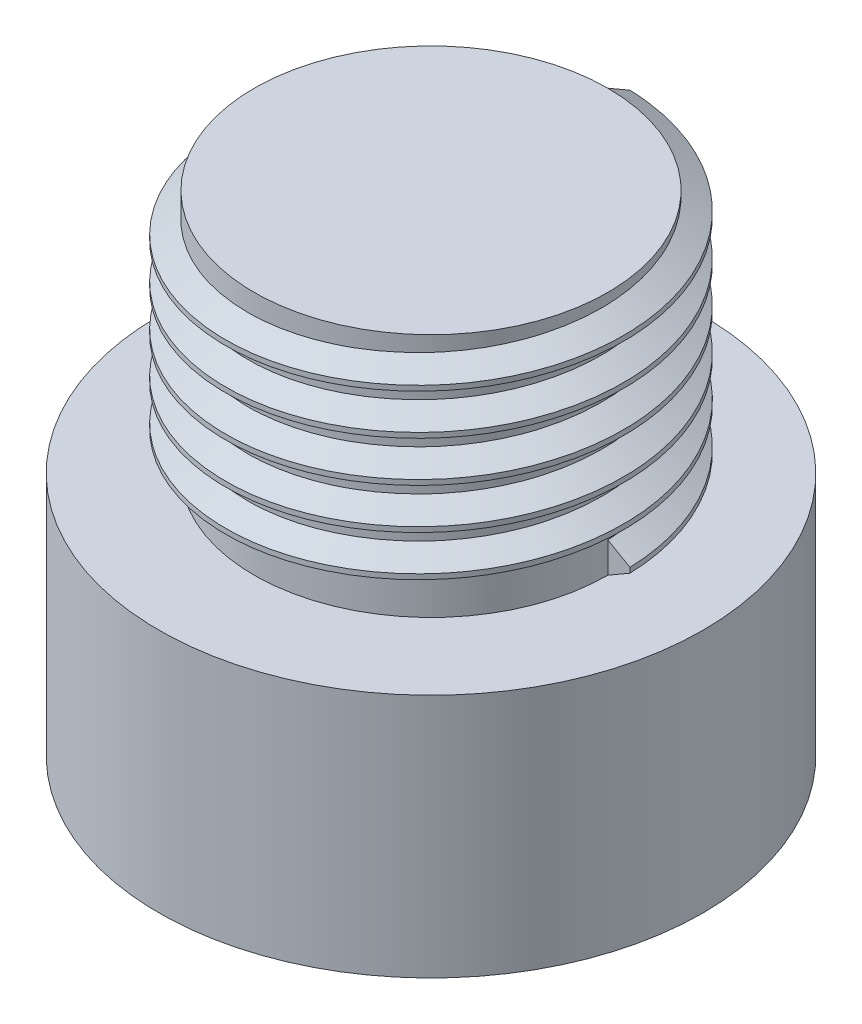
SolidWorks part; units mm, degrees
ref_plane "Спереди" through (0, 0, 0) normal (0, 0, 1) x (1, 0, 0)
ref_plane "Сверху" through (0, 0, 0) normal (0, 1, 0) x (1, 0, 0)
ref_plane "Справа" through (0, 0, 0) normal (1, 0, 0) x (0, 0, -1)
sketch "Эскиз2" plane through (0, 0, 0) normal (0, 0, 1) x (1, 0, 0)
  line L0 (0, 0) -> (0, 14.5)
  line L1 (0, 14.5) -> (-6.5, 14.5)
  line L2 (-6.5, 14.5) -> (-6.5, 5.5)
  line L3 (-6.5, 5.5) -> (-10, 5.5)
  line L4 (-10, 5.5) -> (-10, -3.5)
  line L5 (-10, -3.5) -> (-1.3229, -3.5)
  line L6 (-1.3229, -3.5) -> (-5.2918, 0)
  line L7 (-5.2918, 0) -> (0, 0)
  line L8 (0, 0) -> (0, -4) construction
  line L9 (0, 0) -> (0, -4)
  arc A1 (0, 0) -> (0, -4) centre (0, -2) ccw
  point P11 (-1.3229, -3.5)
  point P13 (0, 0)
  dimension "D2" = 4
  dimension "D8" = 4
  dimension "D1" = 10
  dimension "D3" = 6.5
  dimension "D4" = 18
  dimension "D5" = 14.5
  dimension "D6" = 9
  dimension "D7" = 5.2917
revolve "Повернуть1" add sketch "Эскиз2" angle 360 about L8 region at (-4.5184, 5.0481, 0) region at (-0.8488, -2, 0)
thread "Резьба2" pitch 1.5 method extrude profile "Профиль резьбы2" start angle 0, offset 0, length 0, pitch 1.5, diameter 13
ref_plane "Плоскость5" through (6.5, 5.5, 0) normal (0, 0, 1) x (1, 0, 0)
sketch "Профиль резьбы2" plane through (6.5, 5.5, 0) normal (0, 0, 1) x (1, 0, 0)
  line L0 (0, 0) -> (0, 1.5) construction
  line L1 (0, 0) -> (0.8119, 0.4687)
  line L2 (0.8119, 0.4687) -> (0.8119, 0.6562)
  line L3 (0.8119, 0.6562) -> (0, 1.125)
  line L4 (0.8119, 0.5625) -> (0, 0.5625) construction
  line L11 (0, 0) -> (0, 1.125)
  point P2 (0, 0)
  dimension "Pitch" = 1.5
  dimension "Profile_Angle" = 60
  dimension "Profile_Land" = 0.1875
  dimension "Profile_Height" = 0.8119
